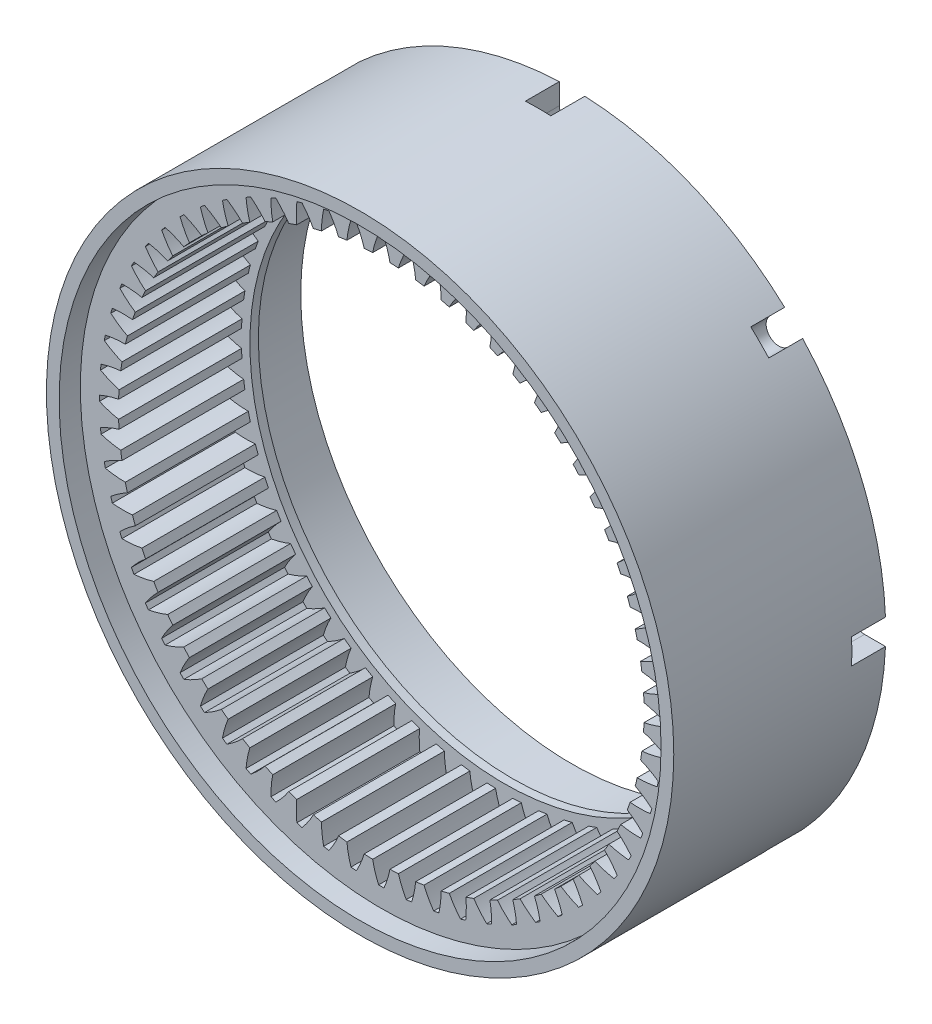
SolidWorks part; units mm, degrees
ref_plane "中间平面" through (0, 0, 0) normal (0, 0, 1) x (1, 0, 0)
ref_plane "上视基准面" through (0, 0, 0) normal (0, 1, 0) x (1, 0, 0)
ref_plane "右视基准面" through (0, 0, 0) normal (1, 0, 0) x (0, 0, -1)
sketch "直内齿圈" plane through (0, 0, 0) normal (0, 0, 1) x (1, 0, 0)
  line L2 (1.1126, 30.0496) -> (0, 0)
  line L3 (0, 0) -> (0, 52) construction
  line L6 (0, 0) -> (-1.1126, 30.0496)
  circle A0 centre (0, 0) radius 30.0702
  circle A1 centre (0, 0) radius 31
  arc A2 (0.7853, 31.9904) -> (-0.7853, 31.9904) centre (0, 0) ccw
  circle A3 centre (0, 0) radius 33.25
  spline S0 degree 4 poles (0.6231, 30.2093) (0.6247, 30.2665) (0.6245, 30.3808) (0.6099, 30.6092) (0.5686, 30.9387) (0.5006, 31.3107) (0.3795, 31.8238) (0.1789, 32.4984) (-0.1334, 33.3335) (-0.7871, 34.7448) (-1.9095, 36.6004) (-3.7891, 38.9795) (-6.6334, 41.6407) (-10.1453, 44.0849) (-14.2563, 46.1708) (-18.5912, 47.7318) (-23.0731, 48.793) (-27.866, 49.4088) (-33.8487, 49.5485) (-40.9565, 48.7992) (-49.0028, 46.7317) (-56.4186, 43.538) (-62.3896, 40.064) (-68.0113, 36.0624) (-72.3853, 32.3212) (-76.4235, 28.2214) (-80.1088, 23.8083) (-82.8395, 20.1071) (-85.9752, 15.2884) (-89.2868, 9.2305) (-92.0249, 2.8875) (-94.1847, -3.6686) (-95.4586, -8.6827) (-96.1644, -12.0587) (-96.6572, -14.8884) (-96.9526, -16.88) (-97.1699, -18.5861) (-97.317, -19.9189) (-97.4097, -20.845) (-97.487, -21.7091) (-97.544, -22.3926) (-97.61, -23.2933) (-97.6524, -23.9388) (-97.7135, -24.9885) (-97.7502, -25.8154) (-97.7971, -27.0328) (-97.8222, -28.1504) (-97.837, -29.3357) (-97.8341, -30.4808) (-97.8242, -31.4154) (-97.7998, -32.5703) (-97.7534, -33.9638) (-97.6846, -35.351) (-97.5943, -36.7409) (-97.5223, -37.6645) (-97.4835, -38.1272) (-97.4633, -38.3579) knots 0 0 0 0 0 0.001401 0.002802 0.005604 0.008133 0.010661 0.015718 0.022839 0.02996 0.048734 0.068727 0.096889 0.125051 0.153212 0.181374 0.209535 0.237696 0.271429 0.327752 0.384075 0.440398 0.46856 0.496721 0.553044 0.581206 0.609367 0.637529 0.66569 0.722013 0.778336 0.806497 0.834659 0.84874 0.86282 0.876901 0.883942 0.890982 0.895509 0.900036 0.904564 0.909091 0.914773 0.920455 0.926136 0.931818 0.943182 0.948864 0.954545 0.960227 0.965909 0.977273 0.988636 0.994318 1 1 1 1 1 construction
  spline S1 degree 4 poles (1.1126, 30.0496) (1.1144, 30.1069) (1.1145, 30.2216) (1.1007, 30.4508) (1.0603, 30.7815) (0.9934, 31.1548) (0.8736, 31.67) (0.6747, 32.3474) (0.3641, 33.1862) (-0.2869, 34.6041) (-1.4067, 36.4695) (-3.2843, 38.8623) (-6.1287, 41.5415) (-9.6437, 44.0053) (-13.7607, 46.1115) (-18.1042, 47.6919) (-22.5968, 48.7716) (-27.4029, 49.4053) (-33.4041, 49.5655) (-40.5369, 48.8375) (-48.6157, 46.7904) (-56.0657, 43.6113) (-62.0674, 40.1463) (-67.7203, 36.1508) (-72.1207, 32.4123) (-76.1855, 28.313) (-79.8972, 23.8982) (-82.6489, 20.1944) (-85.8107, 15.3708) (-89.1531, 9.3048) (-91.9211, 2.9508) (-94.1097, -3.6189) (-95.4044, -8.6447) (-96.1237, -12.029) (-96.6275, -14.8661) (-96.9305, -16.863) (-97.1543, -18.5739) (-97.3063, -19.9104) (-97.4023, -20.8391) (-97.4828, -21.7057) (-97.5286, -22.2339) (-97.5616, -22.6498) (-97.5777, -22.8599) (-97.579, -22.8757) knots 0 0 0 0 0 0.001401 0.002802 0.005604 0.008133 0.010661 0.015718 0.022839 0.02996 0.048734 0.068727 0.096889 0.125051 0.153212 0.181374 0.209535 0.237696 0.271429 0.327752 0.384075 0.440398 0.46856 0.496721 0.553044 0.581206 0.609367 0.637529 0.66569 0.722013 0.778336 0.806497 0.834659 0.84874 0.86282 0.876901 0.883942 0.890982 0.895509 0.900036 0.904564 0.904934 0.904934 0.904934 0.904934 0.904934
  spline S2 degree 4 poles (-0.6231, 30.2093) (-0.6247, 30.2665) (-0.6245, 30.3808) (-0.6099, 30.6092) (-0.5686, 30.9387) (-0.5006, 31.3107) (-0.3795, 31.8238) (-0.1789, 32.4984) (0.1334, 33.3335) (0.7871, 34.7448) (1.9095, 36.6004) (3.7891, 38.9795) (6.6334, 41.6407) (10.1453, 44.0849) (14.2563, 46.1708) (18.5912, 47.7318) (23.0731, 48.793) (27.866, 49.4088) (33.8487, 49.5485) (40.9565, 48.7992) (49.0028, 46.7317) (56.4186, 43.538) (62.3896, 40.064) (68.0113, 36.0624) (72.3853, 32.3212) (76.4235, 28.2214) (80.1088, 23.8083) (82.8395, 20.1071) (85.9752, 15.2884) (89.2868, 9.2305) (92.0249, 2.8875) (94.1847, -3.6686) (95.4586, -8.6827) (96.1644, -12.0587) (96.6572, -14.8884) (96.9526, -16.88) (97.1699, -18.5861) (97.317, -19.9189) (97.4097, -20.845) (97.487, -21.7091) (97.544, -22.3926) (97.61, -23.2933) (97.6524, -23.9388) (97.7135, -24.9885) (97.7502, -25.8154) (97.7971, -27.0328) (97.8222, -28.1504) (97.837, -29.3357) (97.8341, -30.4808) (97.8242, -31.4154) (97.7998, -32.5703) (97.7534, -33.9638) (97.6846, -35.351) (97.5943, -36.7409) (97.5223, -37.6645) (97.4835, -38.1272) (97.4633, -38.3579) knots 0 0 0 0 0 0.001401 0.002802 0.005604 0.008133 0.010661 0.015718 0.022839 0.02996 0.048734 0.068727 0.096889 0.125051 0.153212 0.181374 0.209535 0.237696 0.271429 0.327752 0.384075 0.440398 0.46856 0.496721 0.553044 0.581206 0.609367 0.637529 0.66569 0.722013 0.778336 0.806497 0.834659 0.84874 0.86282 0.876901 0.883942 0.890982 0.895509 0.900036 0.904564 0.909091 0.914773 0.920455 0.926136 0.931818 0.943182 0.948864 0.954545 0.960227 0.965909 0.977273 0.988636 0.994318 1 1 1 1 1 construction
  spline S3 degree 4 poles (-1.1126, 30.0496) (-1.1144, 30.1069) (-1.1145, 30.2216) (-1.1007, 30.4508) (-1.0603, 30.7815) (-0.9934, 31.1548) (-0.8736, 31.67) (-0.6747, 32.3474) (-0.3641, 33.1862) (0.2869, 34.6041) (1.4067, 36.4695) (3.2843, 38.8623) (6.1287, 41.5415) (9.6437, 44.0053) (13.7607, 46.1115) (18.1042, 47.6919) (22.5968, 48.7716) (27.4029, 49.4053) (33.4041, 49.5655) (40.5369, 48.8375) (48.6157, 46.7904) (56.0657, 43.6113) (62.0674, 40.1463) (67.7203, 36.1508) (72.1207, 32.4123) (76.1855, 28.313) (79.8972, 23.8982) (82.6489, 20.1944) (85.8107, 15.3708) (89.1531, 9.3048) (91.9211, 2.9508) (94.1097, -3.6189) (95.4044, -8.6447) (96.1237, -12.029) (96.6275, -14.8661) (96.9305, -16.863) (97.1543, -18.5739) (97.3063, -19.9104) (97.4023, -20.8391) (97.4828, -21.7057) (97.5286, -22.2339) (97.5616, -22.6498) (97.5777, -22.8599) (97.579, -22.8757) knots 0 0 0 0 0 0.001401 0.002802 0.005604 0.008133 0.010661 0.015718 0.022839 0.02996 0.048734 0.068727 0.096889 0.125051 0.153212 0.181374 0.209535 0.237696 0.271429 0.327752 0.384075 0.440398 0.46856 0.496721 0.553044 0.581206 0.609367 0.637529 0.66569 0.722013 0.778336 0.806497 0.834659 0.84874 0.86282 0.876901 0.883942 0.890982 0.895509 0.900036 0.904564 0.904934 0.904934 0.904934 0.904934 0.904934
  point P8 (0, 32)
  dimension "基圆直径" = 60.1403
  dimension "齿顶圆" = 62
  dimension "分度圆" = 64
  dimension "齿根圆" = 66.5
  dimension "D1" = 1.5708
sketch "圆" plane through (0, 0, 0) normal (0, 0, 1) x (1, 0, 0)
  circle A1 centre (0, 0) radius 37
  circle A2 centre (0, 0) radius 31 construction
  circle A3 centre (0, 0) radius 31
  dimension "D1" = 74
extrude "毛胚" add sketch "圆" along normal mid plane 17
chamfer "轮齿倒角" [suppressed] distance 0.001 angle 45
sketch "齿形" plane through (0, 0, 0) normal (0, 0, 1) x (1, 0, 0)
  line L4 (0, 0) -> (-1.1126, 30.0496) construction
  line L5 (1.1126, 30.0496) -> (0, 0) construction
  line L6 (0, 0) -> (-1.1126, 30.0496)
  line L7 (1.1126, 30.0496) -> (0, 0)
  circle A4 centre (0, 0) radius 31 construction
  circle A5 centre (0, 0) radius 33.25 construction
  circle A6 centre (0, 0) radius 31
  circle A7 centre (0, 0) radius 33.25
  spline S1 degree 4 poles (-997.7624, -49.0339) (33.5388, 25.1114) (-0.0477, 25.6108) (-1.3727, 28.223) (-1.0603, 30.7815) (-0.9934, 31.1548) (-0.8736, 31.67) (-0.6747, 32.3474) (-0.3641, 33.1862) (0.2869, 34.6041) (1.4067, 36.4695) (3.2843, 38.8623) (6.1287, 41.5415) (9.6437, 44.0053) (13.7607, 46.1115) (18.1042, 47.6919) (22.5968, 48.7716) (27.4029, 49.4053) (33.4041, 49.5655) (40.5369, 48.8375) (48.6157, 46.7904) (56.0657, 43.6113) (62.0674, 40.1463) (67.7203, 36.1508) (72.1207, 32.4123) (76.1855, 28.313) (79.8972, 23.8982) (82.6489, 20.1944) (85.8107, 15.3708) (89.1531, 9.3048) (91.9211, 2.9508) (94.1097, -3.6189) (95.4044, -8.6447) (96.1237, -12.029) (96.6275, -14.8661) (96.9305, -16.863) (97.1543, -18.5739) (97.3063, -19.9104) (97.4023, -20.8391) (97.4828, -21.7057) (97.7258, -24.5056) (98.0635, -30.3423) (94.9011, 12.6201) (166.7604, -1020.1603) knots -0.054796 -0.054796 -0.054796 -0.054796 -0.054796 0.001401 0.002802 0.005604 0.008133 0.010661 0.015718 0.022839 0.02996 0.048734 0.068727 0.096889 0.125051 0.153212 0.181374 0.209535 0.237696 0.271429 0.327752 0.384075 0.440398 0.46856 0.496721 0.553044 0.581206 0.609367 0.637529 0.66569 0.722013 0.778336 0.806497 0.834659 0.84874 0.86282 0.876901 0.883942 0.890982 0.895509 0.900036 0.904564 0.964947 0.964947 0.964947 0.964947 0.964947 only from (-1.1126, 30.0496) to (97.579, -22.8757) construction
  spline S3 degree 4 poles (997.7624, -49.0339) (-33.5388, 25.1114) (0.0477, 25.6108) (1.3727, 28.223) (1.0603, 30.7815) (0.9934, 31.1548) (0.8736, 31.67) (0.6747, 32.3474) (0.3641, 33.1862) (-0.2869, 34.6041) (-1.4067, 36.4695) (-3.2843, 38.8623) (-6.1287, 41.5415) (-9.6437, 44.0053) (-13.7607, 46.1115) (-18.1042, 47.6919) (-22.5968, 48.7716) (-27.4029, 49.4053) (-33.4041, 49.5655) (-40.5369, 48.8375) (-48.6157, 46.7904) (-56.0657, 43.6113) (-62.0674, 40.1463) (-67.7203, 36.1508) (-72.1207, 32.4123) (-76.1855, 28.313) (-79.8972, 23.8982) (-82.6489, 20.1944) (-85.8107, 15.3708) (-89.1531, 9.3048) (-91.9211, 2.9508) (-94.1097, -3.6189) (-95.4044, -8.6447) (-96.1237, -12.029) (-96.6275, -14.8661) (-96.9305, -16.863) (-97.1543, -18.5739) (-97.3063, -19.9104) (-97.4023, -20.8391) (-97.4828, -21.7057) (-97.7258, -24.5056) (-98.0635, -30.3423) (-94.9011, 12.6201) (-166.7604, -1020.1603) knots -0.054796 -0.054796 -0.054796 -0.054796 -0.054796 0.001401 0.002802 0.005604 0.008133 0.010661 0.015718 0.022839 0.02996 0.048734 0.068727 0.096889 0.125051 0.153212 0.181374 0.209535 0.237696 0.271429 0.327752 0.384075 0.440398 0.46856 0.496721 0.553044 0.581206 0.609367 0.637529 0.66569 0.722013 0.778336 0.806497 0.834659 0.84874 0.86282 0.876901 0.883942 0.890982 0.895509 0.900036 0.904564 0.964947 0.964947 0.964947 0.964947 0.964947 only from (1.1126, 30.0496) to (-97.579, -22.8757) construction
  spline S4 degree 4 poles (-1.1126, 30.0496) (-1.1144, 30.1069) (-1.1145, 30.2216) (-1.1007, 30.4508) (-1.0603, 30.7815) (-0.9934, 31.1548) (-0.8736, 31.67) (-0.6747, 32.3474) (-0.3641, 33.1862) (0.2869, 34.6041) (1.4067, 36.4695) (3.2843, 38.8623) (6.1287, 41.5415) (9.6437, 44.0053) (13.7607, 46.1115) (18.1042, 47.6919) (22.5968, 48.7716) (27.4029, 49.4053) (33.4041, 49.5655) (40.5369, 48.8375) (48.6157, 46.7904) (56.0657, 43.6113) (62.0674, 40.1463) (67.7203, 36.1508) (72.1207, 32.4123) (76.1855, 28.313) (79.8972, 23.8982) (82.6489, 20.1944) (85.8107, 15.3708) (89.1531, 9.3048) (91.9211, 2.9508) (94.1097, -3.6189) (95.4044, -8.6447) (96.1237, -12.029) (96.6275, -14.8661) (96.9305, -16.863) (97.1543, -18.5739) (97.3063, -19.9104) (97.4023, -20.8391) (97.4828, -21.7057) (97.5286, -22.2339) (97.5616, -22.6498) (97.5777, -22.8599) (97.579, -22.8757) knots 0 0 0 0 0 0.001401 0.002802 0.005604 0.008133 0.010661 0.015718 0.022839 0.02996 0.048734 0.068727 0.096889 0.125051 0.153212 0.181374 0.209535 0.237696 0.271429 0.327752 0.384075 0.440398 0.46856 0.496721 0.553044 0.581206 0.609367 0.637529 0.66569 0.722013 0.778336 0.806497 0.834659 0.84874 0.86282 0.876901 0.883942 0.890982 0.895509 0.900036 0.904564 0.904934 0.904934 0.904934 0.904934 0.904934
  spline S5 degree 4 poles (1.1126, 30.0496) (1.1144, 30.1069) (1.1145, 30.2216) (1.1007, 30.4508) (1.0603, 30.7815) (0.9934, 31.1548) (0.8736, 31.67) (0.6747, 32.3474) (0.3641, 33.1862) (-0.2869, 34.6041) (-1.4067, 36.4695) (-3.2843, 38.8623) (-6.1287, 41.5415) (-9.6437, 44.0053) (-13.7607, 46.1115) (-18.1042, 47.6919) (-22.5968, 48.7716) (-27.4029, 49.4053) (-33.4041, 49.5655) (-40.5369, 48.8375) (-48.6157, 46.7904) (-56.0657, 43.6113) (-62.0674, 40.1463) (-67.7203, 36.1508) (-72.1207, 32.4123) (-76.1855, 28.313) (-79.8972, 23.8982) (-82.6489, 20.1944) (-85.8107, 15.3708) (-89.1531, 9.3048) (-91.9211, 2.9508) (-94.1097, -3.6189) (-95.4044, -8.6447) (-96.1237, -12.029) (-96.6275, -14.8661) (-96.9305, -16.863) (-97.1543, -18.5739) (-97.3063, -19.9104) (-97.4023, -20.8391) (-97.4828, -21.7057) (-97.5286, -22.2339) (-97.5616, -22.6498) (-97.5777, -22.8599) (-97.579, -22.8757) knots 0 0 0 0 0 0.001401 0.002802 0.005604 0.008133 0.010661 0.015718 0.022839 0.02996 0.048734 0.068727 0.096889 0.125051 0.153212 0.181374 0.209535 0.237696 0.271429 0.327752 0.384075 0.440398 0.46856 0.496721 0.553044 0.581206 0.609367 0.637529 0.66569 0.722013 0.778336 0.806497 0.834659 0.84874 0.86282 0.876901 0.883942 0.890982 0.895509 0.900036 0.904564 0.904934 0.904934 0.904934 0.904934 0.904934
extrude "插齿" cut sketch "齿形" against normal mid plane 17 contours A6 S5 A7 S4
pattern_circular "圆周阵列" count 64 over 360 about axis through (0, 0, 8.5) along (0, 0, -1) of "插齿"
sketch "分度圆" plane through (0, 0, 0) normal (0, 0, 1) x (1, 0, 0)
  circle A0 centre (0, 0) radius 32 construction
  circle A1 centre (0, 0) radius 32 construction
sketch "草图1" plane through (0, 0, 8.5) normal (0, 0, 1) x (1, 0, 0)
  circle A0 centre (0, 0) radius 35.5
  dimension "D1" = 71
extrude "切除-拉伸1" cut sketch "草图1" against normal blind 2.5
sketch "草图2" plane through (0, 0, -8.5) normal (0, 0, -1) x (-1, 0, 0)
  circle A0 centre (0, 0) radius 37
extrude "凸台-拉伸1" add sketch "草图2" along normal blind 8
sketch "草图3" plane through (0, 0, -8.5) normal (0, 0, 1) x (1, 0, 0)
  circle A0 centre (0, 0) radius 30
  dimension "D1" = 60
extrude "切除-拉伸2" cut sketch "草图3" against normal blind 8
sketch "草图4" plane through (0, 0, -16.5) normal (0, 0, -1) x (-1, 0, 0)
  circle A0 centre (0, 0) radius 32
  dimension "D1" = 64
extrude "切除-拉伸3" cut sketch "草图4" against normal blind 7
sketch "草图5" plane through (0, 0, -16.5) normal (0, 0, -1) x (-1, 0, 0)
  circle A3 centre (0, 0) radius 33
  circle A4 centre (0, 0) radius 33
  dimension "D1" = 1
extrude "切除-拉伸4" cut sketch "草图5" against normal blind 4 flip side to cut
sketch "草图6" plane through (0, 0, -12.5) normal (0, 0, -1) x (-1, 0, 0)
  circle A0 centre (0, 0) radius 37
extrude "拉伸-薄壁1" add sketch "草图6" along normal blind 4 thin thin type one direction reverse wall 1
sketch "草图7" plane through (0, 0, -12.5) normal (0, 0, -1) x (-1, 0, 0)
  line L0 (0, 37) -> (0, 34.5) construction
  line L1 (2.5, 37) -> (2.5, 34.5)
  line L2 (-2.5, 37) -> (-2.5, 34.5)
  circle A0 centre (0, 0) radius 37 construction
  arc A1 (2.5, 37) -> (-2.5, 37) centre (0, 37) ccw
  arc A2 (-2.5, 34.5) -> (2.5, 34.5) centre (0, 34.5) ccw
  point P6 (0, 35.75)
  dimension "D1" = 2.5
  dimension "D2" = 34.5
extrude "凸台-拉伸2" add sketch "草图7" along normal blind 4
sketch "草图8" plane through (0, 0, -16.5) normal (0, 0, -1) x (-1, 0, 0)
  line L4 (1.5, 34.5) -> (1.5, 37)
  line L5 (-1.5, 37) -> (-1.5, 34.5)
  line L6 (1.5, 34.5) -> (1.5, 37)
  line L7 (-1.5, 37) -> (-1.5, 34.5)
  arc A5 (-1.5, 34.5) -> (1.5, 34.5) centre (0, 34.5) ccw
  arc A6 (1.5, 37) -> (-1.5, 37) centre (0, 37) ccw
  arc A7 (-1.5, 34.5) -> (1.5, 34.5) centre (0, 34.5) ccw
  arc A8 (1.5, 37) -> (-1.5, 37) centre (0, 37) ccw
  dimension "D1" = 1
extrude "切除-拉伸5" cut sketch "草图8" against normal blind 4
pattern_circular "阵列(圆周)1" count 8 over 360 about axis through (0, 0, 0) along (0, 0, 1) of "凸台-拉伸2", "切除-拉伸5"
equation "\"D1\"= \"R\""
equation "\"m\" = 1'模数"
equation "\"z\" = 64'齿数"
equation "\"a\"= 20'压力角（常见为20°，一般不用修改）"
equation "\"B\" = 17'齿宽"
equation "\"D\" = 74'大圆值径（必须大于齿根圆，否则自动修正）"
equation "\"d1\"= 0'内径（若设为0或负数，则自动计算）"
equation "\"C1\"= 0'轮齿倒角（若设为0，则无倒角）"
equation "\"x\"= 0'变位系数（不懂勿动）"
equation "\"ha\"= 1'齿顶高系数（不懂勿动）"
equation "\"c\"= 0.25'顶隙系数（不懂勿动）"
equation "\"基圆直径@直内齿圈\" = \"m\" * \"z\" * cos ( \"a\" ) "
equation "\"齿顶圆@直内齿圈\" = IIF ( \"d1\" > 0 , \"d1\" , \"m\" *  ( \"z\" - 2 *  ( \"ha\" + \"x\" )  )  ) "
equation "\"分度圆@直内齿圈\" = \"m\" * \"z\""
equation "\"齿根圆@直内齿圈\" = \"m\" *  ( \"z\" + 2 *  ( \"ha\" + \"x\" + \"c\" )  ) "
equation "\"D1@毛胚\" = \"B\""
equation "\"D1@轮齿倒角\"= IIF ( \"C1\" > 0 , \"C1\" , 0.001 )"
equation "\"轮齿倒角\"= IIF ( \"C1\" > 0 , \"unsuppressed\" , \"suppressed\" )"
equation "\"D1@插齿\" = \"B\""
equation "\"D1@直内齿圈\" = \"m\" *  ( pi / 2 )  - 2 * \"m\" * tan ( \"a\" )  * \"x\""
equation "\"D1@圆周阵列\" = \"z\""
equation "\"D1@圆\"= IIF ( \"D\" > \"m\" * ( \"z\" + 2 * ( \"ha\" + \"x\" + \"c\" ) ) , \"D\" , int ( 1.1 * \"m\" * ( \"z\" + 2 * ( \"ha\" + \"x\" + \"c\" ) ) ) )"
